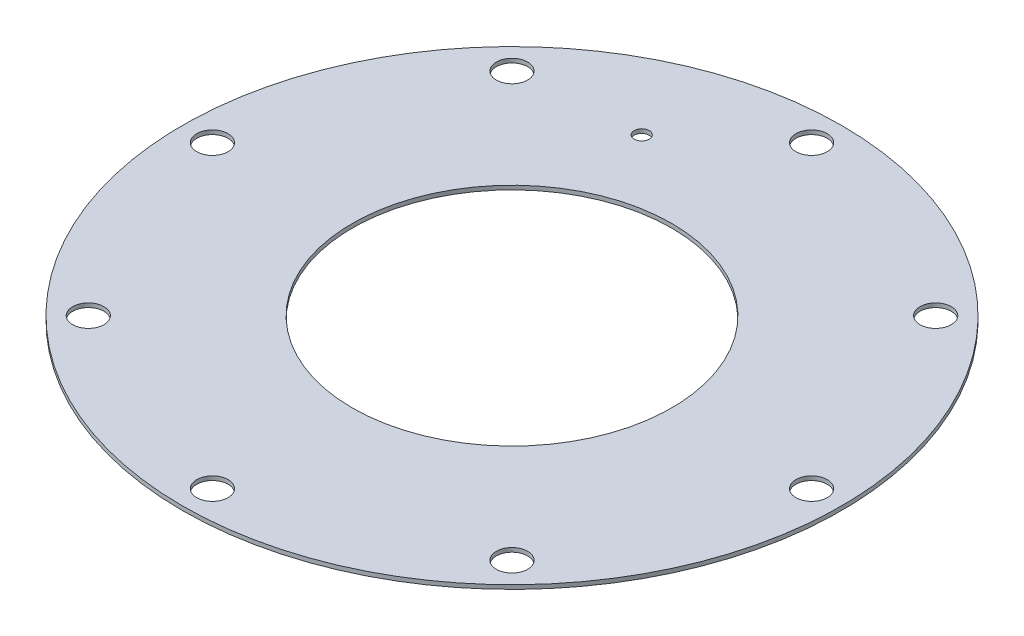
SolidWorks part; units mm, degrees
material "201 Annealed Stainless Steel (SS)"
ref_plane "Front Plane" through (0, 0, 0) normal (0, 0, 1) x (1, 0, 0)
ref_plane "Top Plane" through (0, 0, 0) normal (0, 1, 0) x (1, 0, 0)
ref_plane "Right Plane" through (0, 0, 0) normal (1, 0, 0) x (0, 0, -1)
sketch "Sketch1" plane through (0, 0, 0) normal (0, 1, 0) x (1, 0, 0)
  circle A0 centre (0, 0) radius 69.85
  circle A1 centre (0, 0) radius 33.8636
  circle A2 centre (0, 63.5) radius 3.3147
  circle A3 centre (44.9013, 44.9013) radius 3.3147
  circle A4 centre (63.5, 0) radius 3.3147
  circle A5 centre (44.9013, -44.9013) radius 3.3147
  circle A6 centre (0, -63.5) radius 3.3147
  circle A7 centre (-44.9013, -44.9013) radius 3.3147
  circle A8 centre (-63.5, 0) radius 3.3147
  circle A9 centre (-44.9013, 44.9013) radius 3.3147
  circle A10 centre (-19.4403, 46.9331) radius 1.5875
  point P22 (0, 0)
  dimension "D1" = 6.6294
  dimension "D2" = 67.7272
  dimension "D3" = 139.7
  dimension "D4" = 63.5
  dimension "D6" = 3.175
  dimension "D7" = 22.5
  dimension "D8" = 50.8
  dimension "D5" = 8
extrude "Boss-Extrude1" add sketch "Sketch1" along normal blind 0.8636
